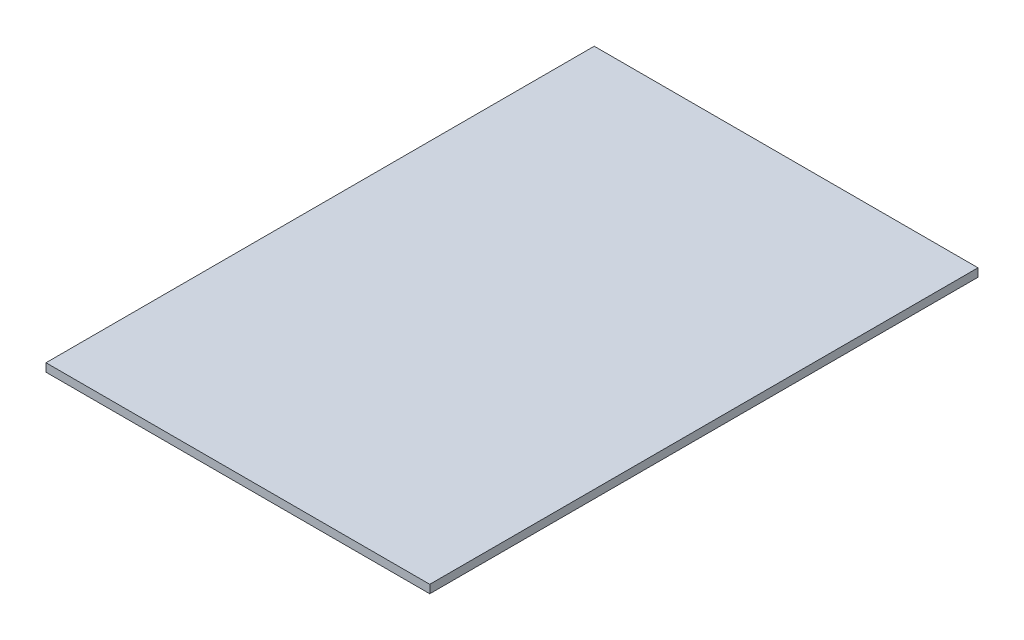
SolidWorks part; units mm, degrees
ref_plane "Front Plane" through (0, 0, 0) normal (0, 0, 1) x (1, 0, 0)
ref_plane "Top Plane" through (0, 0, 0) normal (0, 1, 0) x (1, 0, 0)
ref_plane "Right Plane" through (0, 0, 0) normal (1, 0, 0) x (0, 0, -1)
sketch "Sketch1" plane through (0, 0, 0) normal (0, 1, 0) x (1, 0, 0)
  line L1 (-70, -100) -> (70, -100)
  line L2 (-70, -100) -> (-70, 100)
  line L3 (-70, 100) -> (70, 100)
  line L4 (70, -100) -> (70, 100)
  line L5 (-70, -100) -> (70, 100) construction
  line L6 (-70, 100) -> (70, -100) construction
  point P0 (0, 0)
  dimension "D1" = 140
  dimension "D2" = 200
extrude "Boss-Extrude1" add sketch "Sketch1" along normal blind 3
